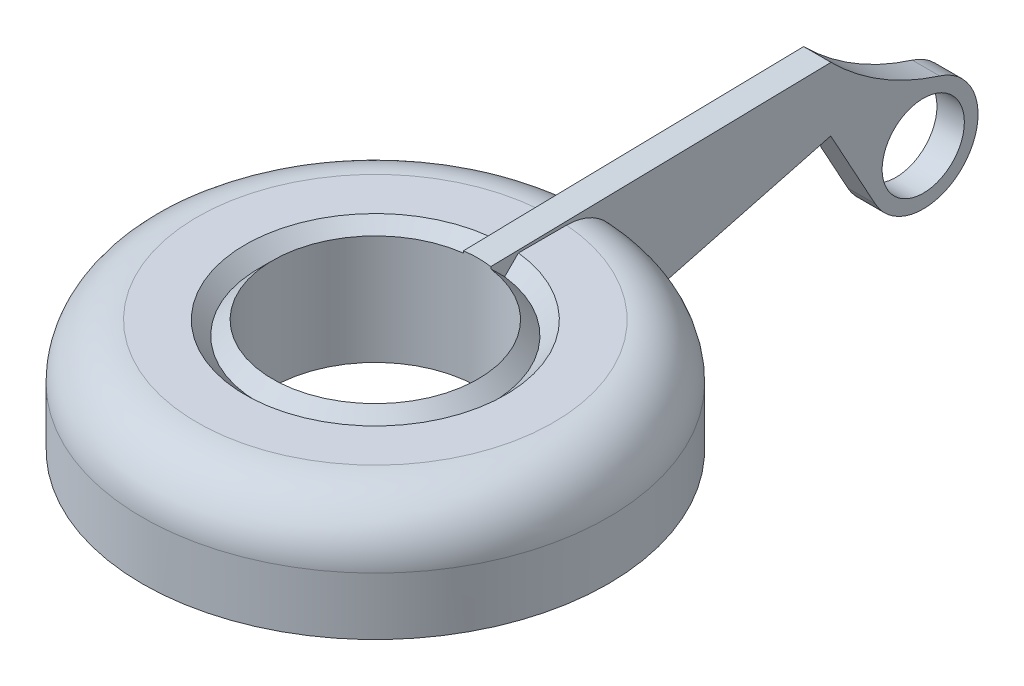
SolidWorks part; units mm, degrees
ref_plane "Front Plane" through (0, 0, 0) normal (0, 0, 1) x (1, 0, 0)
ref_plane "Top Plane" through (0, 0, 0) normal (0, 1, 0) x (1, 0, 0)
ref_plane "Right Plane" through (0, 0, 0) normal (1, 0, 0) x (0, 0, -1)
sketch "Sketch4" plane through (0, 0, 0) normal (1, 0, 0) x (0, 0, -1)
  line L0 (0, 0) -> (-3.75, 0)
  line L1 (-3.75, 0) -> (-4.25, -0.5)
  line L2 (-4.25, -0.5) -> (-4.75, 0)
  line L3 (-4.75, 0) -> (-8.5, 0)
  line L4 (-8.5, 0) -> (-8.5, -4)
  line L5 (-8.5, -4) -> (0, -4)
  line L6 (0, 0) -> (0, -4)
  line L7 (-8.5, -0.5) -> (0, -0.5) construction
  line L8 (0, 1.8905) -> (0, -6.6755) construction
  point P3 (-4.25, -0.5)
  dimension "D1" = 8.5
  dimension "D2" = 0.5
  dimension "D3" = 4
revolve "Revolve1" add sketch "Sketch4" angle 360 about L8
fillet "Fillet1" radius 2 1 edges at (0, 0, 8.5)
sketch "Sketch5" plane through (0, -4, 0) normal (0, -1, 0) x (1, 0, 0)
  circle A0 centre (0, 0) radius 8.5
  circle A1 centre (0, 0) radius 7
  dimension "D1" = 14
extrude "Boss-Extrude1" add sketch "Sketch5" along normal blind 0.1 separate body
sketch "Sketch6" plane through (0, 0, 0) normal (1, 0, 0) x (0, 0, -1)
  line L0 (0, 0) -> (16.1329, 0.32)
  line L1 (8.5, -4) -> (16.1218, -1.9998)
  line L2 (8.5, -4) -> (8.5, -2) construction
  line L3 (8.5, -4) -> (-8.5, -4) construction
  line L4 (16.1218, -1.9998) -> (17.7464, -4.9618)
  line L5 (0, 0) -> (0, -0.9077)
  line L6 (0, -0.9077) -> (7.1744, -0.9077)
  line L7 (7.1744, -0.9077) -> (8.5, -4)
  circle A0 centre (19.5, -4) radius 1.5
  circle A1 centre (19.5, -4) radius 2
  arc A2 (16.1329, 0.32) -> (20.0986, -2.0917) centre (22.992, 7.1325) ccw
  dimension "D1" = 3
  dimension "D2" = 4
  dimension "D3" = 19.5
extrude "Boss-Extrude2" add sketch "Sketch6" along normal blind 0.5 and the other way blind 0.5 contours A2 L0 L5 L6 L7 L1 L4 A1 | A1 A0 region at (0, -1.316, -11.0115) region at (0, -2.8497, -21.0664)
sketch "Sketch7" plane through (0, 0, 0) normal (0, 1, 0) x (1, 0, 0)
  circle A0 centre (0, 0) radius 3.75
  dimension "D1" = 7.5
extrude "Cut-Extrude1" cut sketch "Sketch7" against normal through all both and the other way through all
